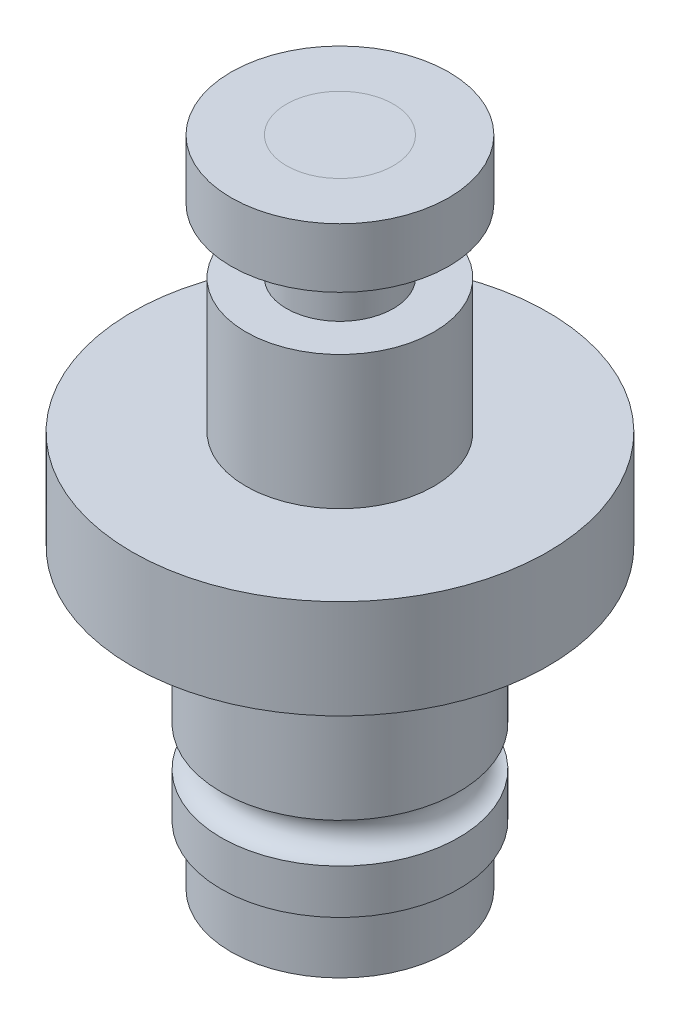
SolidWorks part; units mm, degrees
ref_plane "Front Plane" through (0, 0, 0) normal (0, 0, 1) x (1, 0, 0)
ref_plane "Top Plane" through (0, 0, 0) normal (0, 1, 0) x (1, 0, 0)
ref_plane "Right Plane" through (0, 0, 0) normal (1, 0, 0) x (0, 0, -1)
ref_axis "Axis1" through (0, -29.7184, 0) along (0, 1, 0)
sketch "Sketch1" plane through (0, 0, 0) normal (0, 1, 0) x (1, 0, 0)
  circle A0 centre (0, 0) radius 10.5
  dimension "D1" = 21
extrude "Boss-Extrude1" add sketch "Sketch1" along normal blind 2.5 and the other way blind 2.5
sketch "Sketch2" plane through (0, 2.5, 0) normal (0, 1, 0) x (1, 0, 0)
  circle A0 centre (0, 0) radius 4.75
  dimension "D1" = 9.5
extrude "Boss-Extrude2" add sketch "Sketch2" along normal blind 6.75
sketch "Sketch3" plane through (0, 9.25, 0) normal (0, 1, 0) x (1, 0, 0)
  circle A0 centre (0, 0) radius 2.7
  dimension "D1" = 5.4
extrude "Boss-Extrude4" add sketch "Sketch3" along normal blind 6.25
sketch "Sketch5" plane through (0, 15.5, 0) normal (0, 1, 0) x (1, 0, 0)
  circle A0 centre (0, 0) radius 5.5
  circle A1 centre (0, 0) radius 2.7 construction
  circle A2 centre (0, 0) radius 2.7
  dimension "D1" = 11
extrude "Boss-Extrude5" add sketch "Sketch5" against normal blind 3 separate body
sketch "Sketch6" plane through (0, -2.5, 0) normal (0, -1, 0) x (1, 0, 0)
  circle A0 centre (0, 0) radius 2.5
  dimension "D1" = 5
extrude "Boss-Extrude6" add sketch "Sketch6" along normal blind 15 separate body
sketch "Sketch7" plane through (0, -2.5, 0) normal (0, -1, 0) x (1, 0, 0)
  circle A0 centre (0, 0) radius 4.875
  circle A1 centre (0, 0) radius 2.5 construction
  circle A2 centre (0, 0) radius 2.5
  dimension "D1" = 9.75
extrude "Boss-Extrude7" add sketch "Sketch7" along normal blind 1 separate body
sketch "Sketch8" plane through (0, -3.5, 0) normal (0, -1, 0) x (1, 0, 0)
  circle A0 centre (0, 0) radius 6
  circle A1 centre (0, 0) radius 2.5 construction
  circle A2 centre (0, 0) radius 2.5
  dimension "D1" = 12
extrude "Boss-Extrude8" add sketch "Sketch8" along normal blind 11 separate body
sketch "Sketch9" plane through (0, 0, 0) normal (0, 0, 1) x (1, 0, 0)
  line L0 (6, -14.5) -> (6, -3.5) construction
  circle A0 centre (6, -11.25) radius 1
  dimension "D2" = 2
  dimension "D1" = 3.25
revolve "Cut-Revolve1" cut sketch "Sketch9" angle 360 about axis through (0, -29.7184, 0) along (0, 1, 0)
sketch "Sketch10" plane through (0, -14.5, 0) normal (0, -1, 0) x (1, 0, 0)
  circle A0 centre (0, 0) radius 5.5
  circle A1 centre (0, 0) radius 2.5 construction
  circle A2 centre (0, 0) radius 2.5
  dimension "D1" = 11
extrude "Boss-Extrude12" add sketch "Sketch10" along normal blind 3 separate body
sketch "Sketch12" plane through (0, 0, 0) normal (0, 0, 1) x (1, 0, 0)
  line L0 (0, -17.5) -> (0, -11.25)
  line L1 (-5.5, -17.5) -> (5.5, -17.5) construction
  line L2 (0, -11.25) -> (0, 15.5)
  line L3 (5.5, 15.5) -> (-5.5, 15.5) construction
  line L4 (0, -11.25) -> (6, -11.25)
  line L5 (6, -10.25) -> (6, -12.25)
  line L6 (0, 0) -> (-14.31, 0)
  line L7 (-14.31, 5.65) -> (-14.31, -5.65) construction
  line L8 (-14.31, 0) -> (-15.31, 0)
  line L9 (-14.31, 5.65) -> (-15.31, 5.65)
  line L10 (-14.31, -5.65) -> (-15.31, -5.65)
  line L11 (-15.31, 5.65) -> (-15.31, -5.65) construction
  line L12 (-5.5, 15.5) -> (-5.5, 12.5) construction
  line L14 (-4.75, 9.25) -> (-4.75, 2.5) construction
  line L15 (-10.5, 2.5) -> (-10.5, -2.5) construction
  line L18 (-6, -3.5) -> (-6, -10.25) construction
  line L19 (-5.5, -14.5) -> (-5.5, -17.5) construction
  line L20 (-5.5, 12.5) -> (5.5, 12.5) construction
  arc A0 (-14.31, 5.65) -> (-14.31, -5.65) centre (-14.31, 0) cw
  arc A1 (-15.31, 5.65) -> (-15.31, -5.65) centre (-15.31, 0) ccw
  dimension "D4" = 6
  dimension "D1" = 14.31
  dimension "D2" = 11.3
  dimension "D3" = 1
  dimension "D5" = 6.25
  dimension "D6" = 11.25
  dimension "D7" = 15.5
  dimension "D8" = 5.5
  dimension "D9" = 4.75
  dimension "D10" = 10.5
  dimension "D11" = 6
  dimension "D12" = 5.5
  dimension "D13" = 3
